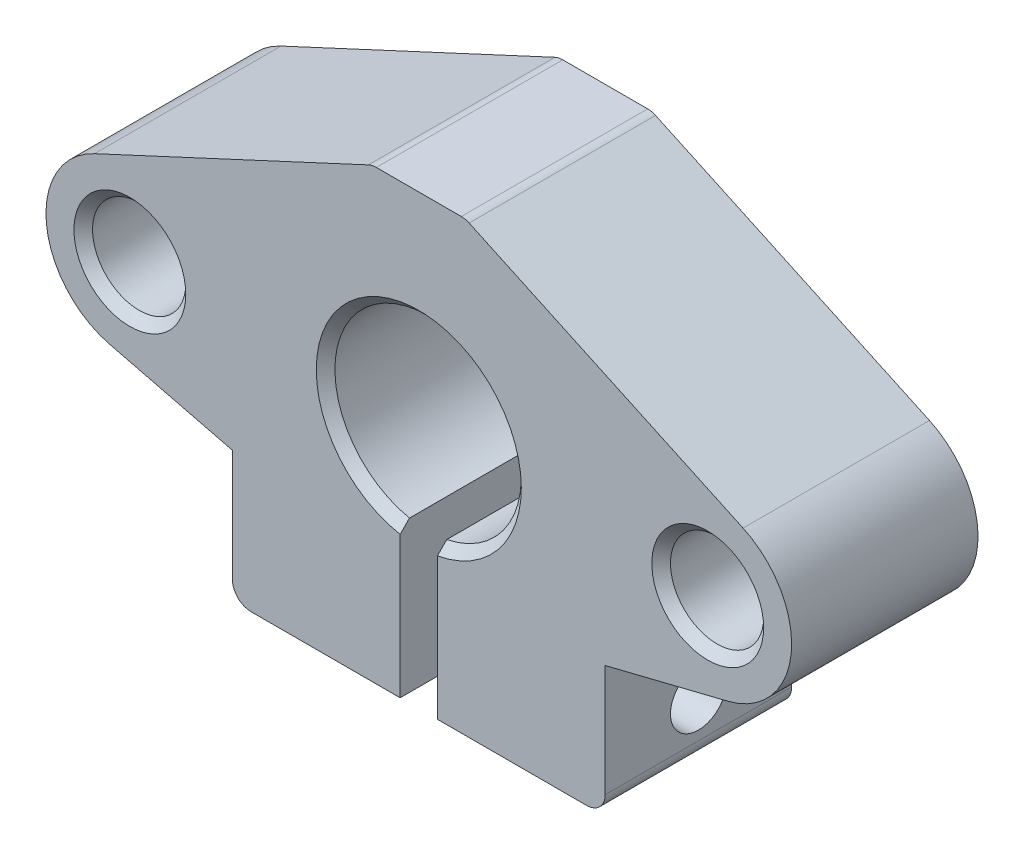
SolidWorks part; units mm, degrees
material "1060 合金"
ref_plane "前视基准面" through (0, 0, 0) normal (0, 0, 1) x (1, 0, 0)
ref_plane "上视基准面" through (0, 0, 0) normal (0, 1, 0) x (1, 0, 0)
ref_plane "右视基准面" through (0, 0, 0) normal (1, 0, 0) x (0, 0, -1)
other "Configuration Table"
sketch "草图1" plane through (0, 0, 0) normal (0, 0, 1) x (1, 0, 0)
  line L0 (0, 0) -> (0, 8)
  line L1 (0, 24) -> (-2.5, 24)
  line L2 (-2.5, 24) -> (-17.3957, 17.0812)
  line L4 (-16.583, 8.6323) -> (-10, 7)
  line L5 (-10, 7) -> (-10, 0)
  line L6 (-10, 0) -> (0, 0)
  line L7 (0, 18) -> (0, 24)
  arc A0 (0, 18) -> (0, 8) centre (0, 13) ccw
  circle A1 centre (-15.5, 13) radius 2.5
  arc A2 (-17.3957, 17.0812) -> (-16.583, 8.6323) centre (-15.5, 13) ccw
  point P12 (0, 0)
  point P14 (-8.2498, 22.4602)
  dimension "D3" = 10
  dimension "D4" = 5
  dimension "D9" = 4.5
  dimension "D1" = 10
  dimension "D2" = 7
  dimension "D5" = 15.5
  dimension "D6" = 13
  dimension "D7" = 2.5
  dimension "D8" = 24
extrude "凸台-拉伸1" add sketch "草图1" along normal blind 10
mirror "镜向1" about plane through (0, 18, 10) normal (-1, 0, 0) of "凸台-拉伸1"
sketch "草图2" plane through (0, 0, 0) normal (0, -1, 0) x (1, 0, 0)
  line L0 (-10, 10) -> (10, 10) construction
  line L1 (-1, 10) -> (1, 10)
  line L2 (-1, 10) -> (-1, 0)
  line L3 (-1, 0) -> (1, 0)
  line L4 (1, 10) -> (1, 0)
  line L5 (-10, 0) -> (10, 0) construction
  dimension "D1" = 2
  dimension "D2" = 1
extrude "切除-拉伸1" cut sketch "草图2" against normal blind 10
sketch "草图3" plane through (10, 0, 0) normal (1, 0, 0) x (0, 0, -1)
  line L0 (-10, 7) -> (-10, 0) construction
  line L1 (-10, 0) -> (0, 0) construction
  circle A0 centre (-5, 3) radius 1.5
  dimension "D1" = 3
  dimension "D2" = 5
  dimension "D3" = 3
extrude "切除-拉伸2" cut sketch "草图3" against normal through all
chamfer "倒角1" distance 0.5 angle 45 7 edges at (-10, 3, 3.5) (13, 13, 0) (0, 18, 0) (-13, 13, 0) (13, 13, 10) (-13, 13, 10) (0, 18, 10)
fillet "圆角1" radius 1 4 edges at (-2.5, 24, 5) (2.5, 24, 5) (-10, 0, 5) (10, 0, 5)
